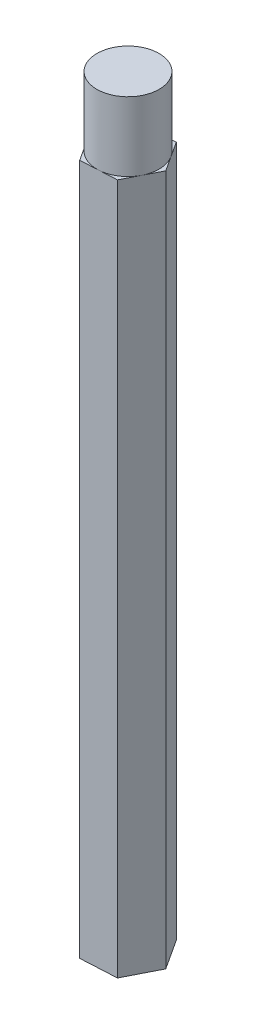
SolidWorks part; units mm, degrees
ref_plane "Front Plane" through (0, 0, 0) normal (0, 0, 1) x (1, 0, 0)
ref_plane "Top Plane" through (0, 0, 0) normal (0, 1, 0) x (1, 0, 0)
ref_plane "Right Plane" through (0, 0, 0) normal (1, 0, 0) x (0, 0, -1)
sketch "Sketch1" plane through (0, 0, 0) normal (0, 1, 0) x (1, 0, 0)
  line L1 (1.4388, -2.213) -> (2.636, 0.1395)
  line L2 (2.636, 0.1395) -> (1.1971, 2.3526)
  line L3 (1.1971, 2.3526) -> (-1.4388, 2.213)
  line L4 (-1.4388, 2.213) -> (-2.636, -0.1395)
  line L5 (-2.636, -0.1395) -> (-1.1971, -2.3526)
  line L6 (-1.1971, -2.3526) -> (1.4388, -2.213)
  circle A0 centre (0, 0) radius 2.286 construction
  circle A1 centre (0, 0) radius 2.286
  dimension "D2" = 2.3526
  dimension "D1" = 4.572
extrude "Boss-Extrude1" add sketch "Sketch1" along normal blind 50.8 contours A1 L6 L1 | A1 L5 L6 | A1 | A1 L1 L2 | A1 L2 L3 | L3 L4 L5 L6 L1 L2 region at (1.2879, 0, 1.9809) region at (2.3594, 0, -0.1249) region at (0, 0, 0) region at (-1.0715, 0, 2.1058) region at (1.0715, 0, -2.1058)
extrude "Boss-Extrude2" add sketch "Sketch1<3>" along normal blind 55.88 contours A1
sketch "Sketch1<3>" plane through (0, 0, 0) normal (0, 1, 0) x (1, 0, 0) same geometry as "Sketch1"
